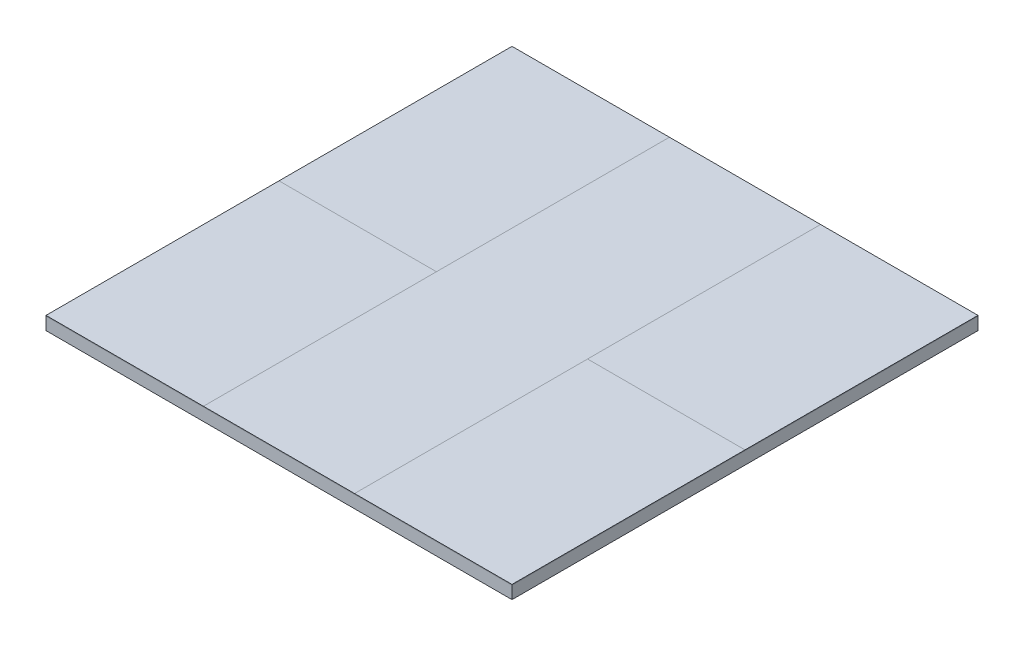
SolidWorks part; units mm, degrees
ref_plane "Front Plane" through (0, 0, 0) normal (0, 0, 1) x (1, 0, 0)
ref_plane "Top Plane" through (0, 0, 0) normal (0, 1, 0) x (1, 0, 0)
ref_plane "Right Plane" through (0, 0, 0) normal (1, 0, 0) x (0, 0, -1)
sketch "Sketch1" plane through (0, 0, 0) normal (0, 1, 0) x (1, 0, 0)
  line L1 (37, -37) -> (-37, -37)
  line L2 (37, -37) -> (37, 37)
  line L3 (37, 37) -> (-37, 37)
  line L4 (-37, -37) -> (-37, 37)
  line L5 (37, -37) -> (-37, 37) construction
  line L6 (37, 37) -> (-37, -37) construction
  point P0 (0, 0)
  dimension "D1" = 74
  dimension "D2" = 74
extrude "Boss-Extrude1" add sketch "Sketch1" along normal blind 2
sketch "Sketch2" plane through (0, 2, 0) normal (0, 1, 0) x (1, 0, 0)
  line L0 (-37, -37) -> (37, -37) construction
  line L1 (-37, 37) -> (-12, 37)
  line L2 (-37, 37) -> (-37, -37)
  line L3 (-37, -37) -> (-12, -37)
  line L4 (-12, 37) -> (-12, -37)
  line L5 (-37, 0) -> (-12, 0)
  line L6 (-12, 37) -> (12, 37)
  line L7 (-12, 37) -> (-12, -37)
  line L8 (-12, -37) -> (12, -37)
  line L9 (12, 37) -> (12, -37)
  line L10 (12, 37) -> (37, 37)
  line L11 (12, 37) -> (12, -37)
  line L12 (12, -37) -> (37, -37)
  line L13 (37, 37) -> (37, -37)
  line L14 (12, 0) -> (37, 0)
  line M1 (-37, 37) -> (-37, -37)
  line M2 (-37, -37) -> (37, -37)
  line M3 (37, -37) -> (37, 37)
  line M4 (37, 37) -> (-37, 37)
  dimension "D1" = 25
  dimension "D2" = 25
extrude "Boss-Extrude2" add sketch "Sketch2" along normal blind 0.1 separate body contours L5 L4 M1 M4 region at (-24.5, 2, -18.5)
extrude "Boss-Extrude3" add sketch "Sketch2<3>" along normal blind 0.1 separate body contours L14 L11 M2 M3 region at (24.5, 2, 18.5)
sketch "Sketch2<3>" plane through (0, 2, 0) normal (0, 1, 0) x (1, 0, 0) same geometry as "Sketch2"
extrude "Boss-Extrude4" add sketch "Sketch2<4>" along normal blind 0.1 separate body contours L5 L2 L4 M2 region at (-24.5, 2, 18.5)
sketch "Sketch2<4>" plane through (0, 2, 0) normal (0, 1, 0) x (1, 0, 0) same geometry as "Sketch2"
extrude "Boss-Extrude5" add sketch "Sketch2<5>" along normal blind 0.1 separate body contours L9 L4 L11 M4 M2 region at (0, 2, 0)
sketch "Sketch2<5>" plane through (0, 2, 0) normal (0, 1, 0) x (1, 0, 0) same geometry as "Sketch2"
extrude "Boss-Extrude6" add sketch "Sketch2<6>" along normal blind 0.1 separate body contours L9 L14 L13 M4 region at (24.5, 2, -18.5)
sketch "Sketch2<6>" plane through (0, 2, 0) normal (0, 1, 0) x (1, 0, 0) same geometry as "Sketch2"
